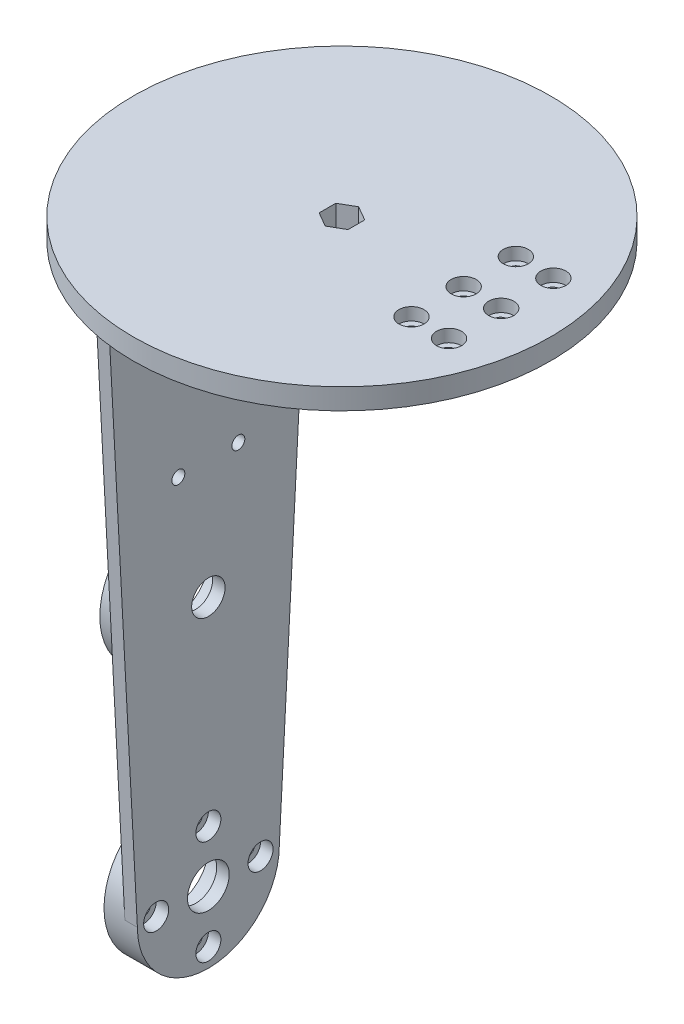
SolidWorks part; units mm, degrees
ref_plane "Front Plane" through (0, 0, 0) normal (0, 0, 1) x (1, 0, 0)
ref_plane "Top Plane" through (0, 0, 0) normal (0, 1, 0) x (1, 0, 0)
ref_plane "Right Plane" through (0, 0, 0) normal (1, 0, 0) x (0, 0, -1)
sketch "Sketch2" plane through (0, 0, 0) normal (0, 1, 0) x (1, 0, 0)
  circle A0 centre (0, 0) radius 9
extrude "Boss-Extrude1" add sketch "Sketch2" along normal blind 20
sketch "Sketch3" plane through (0, 20, 0) normal (0, 1, 0) x (1, 0, 0)
  line L0 (-3.4641, -2) -> (3.4641, 2) construction
  line L1 (0, -4) -> (0, 4) construction
  line L2 (3.4641, -2) -> (-3.4641, 2) construction
  line L15 (0, 4) -> (-3.4641, 2)
  line L16 (-3.4641, 2) -> (-3.4641, -2)
  line L17 (-3.4641, -2) -> (0, -4)
  line L18 (0, -4) -> (3.4641, -2)
  line L19 (3.4641, -2) -> (3.4641, 2)
  line L20 (3.4641, 2) -> (0, 4)
  circle A0 centre (0, 0) radius 4 construction
  point P4 (0, 0)
  point P5 (0, 0)
  point P6 (0, 0)
  point P9 (0, 0)
  point P10 (0, 0)
  point P11 (0, 0)
  point P14 (0, 0)
  point P15 (0, 0)
  point P17 (0, 0)
  point P20 (0, 0)
extrude "Cut-Extrude1" cut sketch "Sketch3" against normal blind 20
sketch "Sketch4" plane through (0, 20, 0) normal (0, 1, 0) x (1, 0, 0)
  circle A0 centre (0, 0) radius 50
  circle A1 centre (0, 0) radius 4.5
extrude "Boss-Extrude3" add sketch "Sketch4" against normal blind 5
ref_plane "Plane3" through (0, 0, 0) normal (0.5, 0, 0.866) x (0.866, 0, -0.5)
sketch "Sketch11" plane through (0, 0, 0) normal (0.5, 0, 0.866) x (0.866, 0, -0.5)
  line L2 (0, 0) -> (0, 5) construction
  circle A0 centre (0, 5) radius 1.55
extrude "Cut-Extrude2" cut sketch "Sketch11" against normal blind 9 and the other way blind 9
ref_plane "Plane4" through (0, 0, 0) normal (1, 0, 0) x (0, 0, -1)
sketch "Sketch15" plane through (0, 0, 0) normal (1, 0, 0) x (0, 0, -1)
  line L0 (0, 0) -> (0, 9) construction
  circle A0 centre (0, 9) radius 1.55
extrude "Cut-Extrude9" cut sketch "Sketch15" against normal blind 9 and the other way blind 9
sketch "Sketch16" plane through (0, 15, 0) normal (0, -1, 0) x (1, 0, 0)
  line L0 (0, 0) -> (32, 0) construction
  line L6 (0, 0) -> (-32, 0) construction
  line L7 (-32, -25) -> (-32, 25) construction
  line L8 (32, 25) -> (32, -25) construction
  line L9 (32, 25) -> (35, 25) construction
  line L10 (32, -25) -> (35, -25) construction
  line L11 (35, 25) -> (35, -25) construction
  line L12 (32, 25) -> (35, -25) construction
  line L13 (32, -25) -> (35, 25) construction
  line L14 (32, 25) -> (26.3083, 25) construction
  line L15 (35, 25) -> (41, 25) construction
  line L16 (29.1541, 25) -> (29.1541, 12.5) construction
  line L17 (29.1541, 12.5) -> (29.1541, 0) construction
  line L18 (29.1541, 0) -> (29.1541, -12.5) construction
  line L19 (38, 25) -> (38, 12.5) construction
  line L20 (38, 12.5) -> (38, 0) construction
  line L21 (38, 0) -> (38, -12.5) construction
  circle A0 centre (29.1541, 12.5) radius 1.55
  circle A1 centre (29.1541, 0) radius 1.55
  circle A2 centre (29.1541, -12.5) radius 1.55
  circle A3 centre (38, -12.5) radius 1.55
  circle A4 centre (38, 0) radius 1.55
  circle A5 centre (38, 12.5) radius 1.55
  point P8 (32, 0)
  point P10 (-32, 0)
  point P14 (33.5, 0)
ref_plane "Plane7" through (-32, 0, 0) normal (-1, 0, 0) x (0, 0, 1)
sketch "Sketch28" plane through (-32, 0, 0) normal (-1, 0, 0) x (0, 0, 1)
  line L0 (25, 15) -> (-25, 15)
  line L1 (0, -135) -> (0, -75) construction
  line L2 (-50, 15) -> (50, 15) construction
  line L3 (0, 15) -> (0, -135) construction
  line L6 (25, 15) -> (17, -135)
  line L7 (-17, -135) -> (-25, 15)
  circle A0 centre (0, -135) radius 5
  circle A3 centre (0, -75) radius 4
  arc A6 (17, -135) -> (-17, -135) centre (0, -135) cw
  circle A8 centre (7.1867, -46.5) radius 1.55
  circle A9 centre (-7.1867, -46.5) radius 1.55
  point P4 (0, 15)
extrude "Boss-Extrude10" add sketch "Sketch28" along normal blind 3
sketch "Sketch25" plane through (-35, 0, 0) normal (-1, 0, 0) x (0, 0, 1)
  circle A6 centre (0, -135) radius 8
  circle A7 centre (0, -135) radius 17
extrude "Boss-Extrude8" add sketch "Sketch25" along normal blind 5
sketch "Sketch26" plane through (-40, 0, 0) normal (-1, 0, 0) x (0, 0, 1)
  circle A12 centre (0, -135) radius 12.5 construction
  circle A16 centre (-12.5, -135) radius 1.55
  circle A17 centre (0, -122.5) radius 1.55
  circle A18 centre (12.5, -135) radius 1.55
  circle A19 centre (0, -147.5) radius 1.55
  point P14 (0, -135)
extrude "Cut-Extrude14" cut sketch "Sketch26" against normal blind 8
sketch "Sketch27" plane through (-32, 0, 0) normal (1, 0, 0) x (0, 0, -1)
  circle A4 centre (0, -135) radius 12.5 construction
  circle A5 centre (-12.5, -135) radius 3
  circle A6 centre (0, -122.5) radius 3
  circle A7 centre (12.5, -135) radius 3
  circle A8 centre (0, -147.5) radius 3
  point P15 (0, -135)
extrude "Cut-Extrude15" cut sketch "Sketch27" against normal blind 3
extrude "Cut-Extrude17" cut sketch "Sketch16" against normal blind 5
sketch "Sketch29" plane through (0, 20, 0) normal (0, 1, 0) x (1, 0, 0)
  circle A0 centre (29.1541, 12.5) radius 3
  circle A1 centre (38.1541, 12.5) radius 3
  circle A2 centre (38.1541, 0) radius 3
  circle A3 centre (38.1541, -12.5) radius 3
  circle A4 centre (29.1541, 0) radius 3
  circle A5 centre (29.1541, -12.5) radius 3
  dimension "D1" = 2
  dimension "D2" = 3
extrude "Cut-Extrude18" cut sketch "Sketch29" against normal blind 3
sketch "Sketch30" plane through (-35, 0, 0) normal (-1, 0, 0) x (0, 0, 1)
  circle A0 centre (0, -75) radius 9.5
  circle A1 centre (0, -75) radius 17
extrude "Boss-Extrude11" add sketch "Sketch30" along normal blind 6
sketch "Sketch31" plane through (0, 0, 0) normal (0.5, 0, 0.866) x (0.866, 0, -0.5)
  circle A1 centre (0, 5) radius 3
extrude "Cut-Extrude23" cut sketch "Sketch31" against normal blind 2.5 from offset 9
extrude "Cut-Extrude24" cut sketch "Sketch31<3>" along normal blind 2.5 from offset 9 offset against normal yes
sketch "Sketch31<3>" plane through (0, 0, 0) normal (0.5, 0, 0.866) x (0.866, 0, -0.5) same geometry as "Sketch31"
sketch "Sketch33" plane through (0, 0, 0) normal (1, 0, 0) x (0, 0, -1)
  circle A0 centre (0, 9) radius 3
extrude "Cut-Extrude25" cut sketch "Sketch33" against normal blind 2.5 from offset 9
extrude "Cut-Extrude26" cut sketch "Sketch33<2>" along normal blind 2.5 from offset 9 offset against normal yes
sketch "Sketch33<2>" plane through (0, 0, 0) normal (1, 0, 0) x (0, 0, -1) same geometry as "Sketch33"
